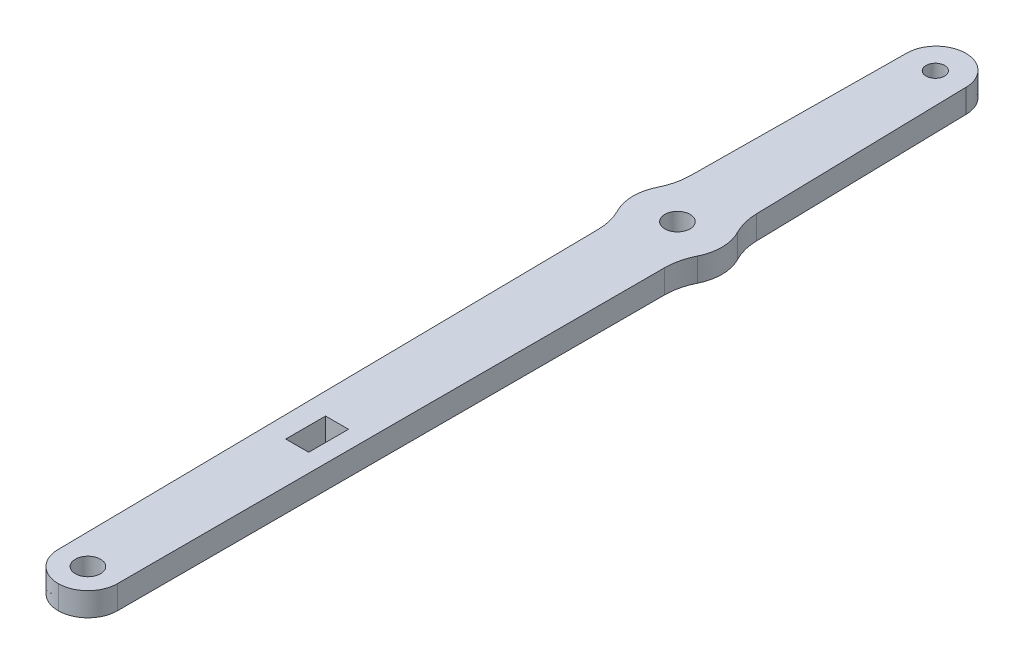
SolidWorks part; units mm, degrees
material "Acrylic (Medium-high impact)"
ref_plane "Front Plane" through (0, 0, 0) normal (0, 0, 1) x (1, 0, 0)
ref_plane "Top Plane" through (0, 0, 0) normal (0, 1, 0) x (1, 0, 0)
ref_plane "Right Plane" through (0, 0, 0) normal (1, 0, 0) x (0, 0, -1)
sketch "Sketch1" plane through (0, 0, 0) normal (0, 1, 0) x (1, 0, 0)
  line L0 (7.7577, 53.7567) -> (7.7577, 53.6568)
  line L1 (7.7577, 53.6568) -> (8.4096, 24.8453)
  line L2 (8.5133, 12.3124) -> (8.5133, -61.4358)
  line L3 (0.5279, -61.4885) -> (-0.4396, 12.2123)
  line L4 (3.7656, 54.891) -> (3.7656, 52.2411) construction
  line L5 (-1.3686, 21.2305) -> (-1.3539, 21.2643)
  line L6 (-0.5009, 24.7866) -> (-0.2271, 53.6041)
  line L7 (-0.2271, 53.6041) -> (-0.2271, 53.7041)
  line L8 (2.4981, 18.5655) -> (5.4926, 18.5655) construction
  line L9 (4.5203, -59.9358) -> (4.5205, -62.9357) construction
  line L225 (6.0675, -33.2244) -> (6.0675, -27.8508)
  line L226 (6.0675, -27.8508) -> (2.9734, -27.8508)
  line L227 (2.9734, -27.8508) -> (2.9734, -33.2244)
  line L228 (2.9734, -33.2244) -> (6.0675, -33.2244)
  circle A0 centre (4.5204, -61.4358) radius 1.7
  circle A1 centre (3.9954, 18.5655) radius 1.7
  circle A2 centre (3.7656, 53.5661) radius 1.25
  spline S6 degree 3 poles (8.4096, 24.8453) (8.4374, 23.6215) (8.7449, 22.4205) (9.309, 21.3347) knots 2 2 2 2 3 3 3 3
  spline S7 degree 3 poles (9.309, 21.3347) (10.1939, 19.6303) (10.2107, 17.6044) (9.3541, 15.8856) knots 3 3 3 3 4 4 4 4
  spline S8 degree 3 poles (9.3541, 15.8856) (8.8012, 14.7758) (8.5133, 13.5526) (8.5133, 12.3124) knots 4 4 4 4 5 5 5 5
  spline S9 degree 3 poles (8.5133, -61.4358) (8.5133, -63.6346) (6.7417, -65.4213) (4.5467, -65.4358) knots 6 6 6 6 7 7 7 7
  spline S10 degree 3 poles (4.5467, -65.4358) (2.3516, -65.4501) (0.5567, -63.6872) (0.5279, -61.4885) knots 7 7 7 7 8 8 8 8
  spline S11 degree 3 poles (-0.4396, 12.2123) (-0.445, 13.4525) (-0.7383, 14.6747) (-1.296, 15.7819) knots 9 9 9 9 10 10 10 10
  spline S12 degree 3 poles (-1.296, 15.7819) (-2.1897, 17.4818) (-2.2167, 19.5075) (-1.3686, 21.2305) knots 11 11 11 11 12 12 12 12
  spline S13 degree 3 poles (-1.3539, 21.2643) (-0.8045, 22.3575) (-0.5127, 23.5626) (-0.5009, 24.7866) knots 13 13 13 13 14 14 14 14
  spline S14 degree 3 poles (-0.2271, 53.7041) (-0.2065, 55.8882) (1.5591, 57.6517) (3.7394, 57.6661) knots 16 16 16 16 17 17 17 17
  spline S15 degree 3 poles (3.7394, 57.6661) (5.9195, 57.6805) (7.7081, 55.9402) (7.7577, 53.7567) knots 17 17 17 17 18 18 18 18
  dimension "D1" = 3.4
  dimension "D2" = 2.5
extrude "Boss-Extrude1" add sketch "Sketch1" along normal blind 3.175
